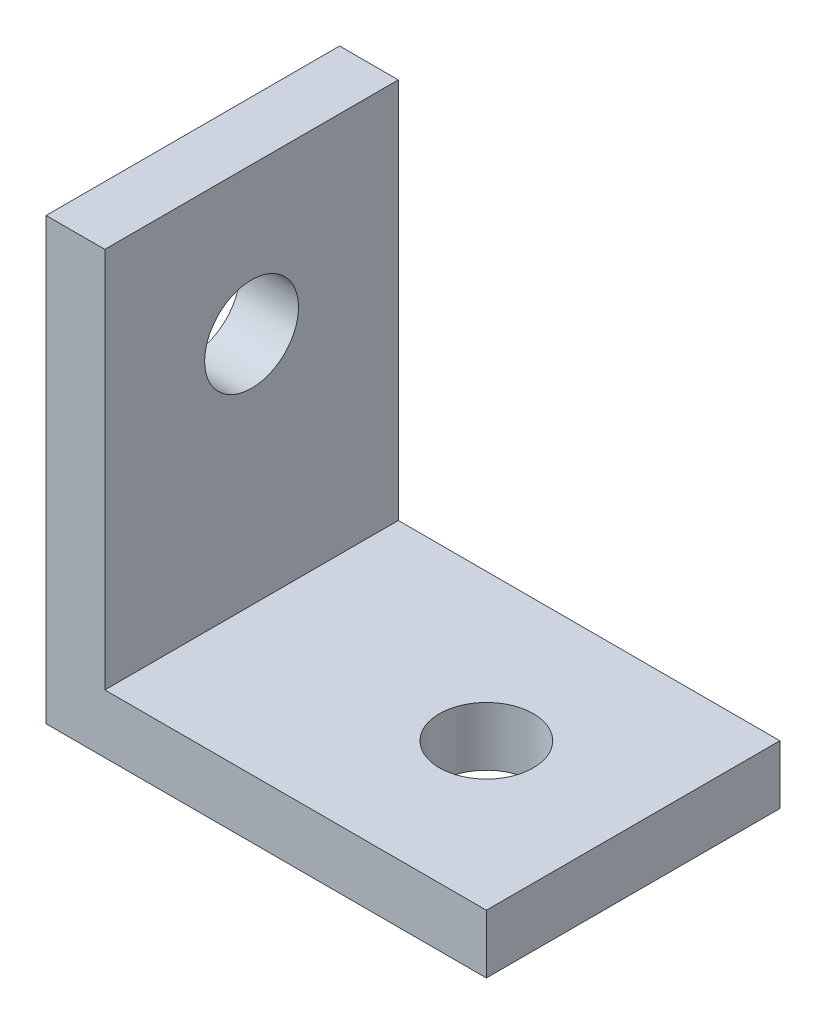
SolidWorks part; units mm, degrees
material "1060 Alloy"
ref_plane "Front Plane" through (0, 0, 0) normal (0, 0, 1) x (1, 0, 0)
ref_plane "Top Plane" through (0, 0, 0) normal (0, 1, 0) x (1, 0, 0)
ref_plane "Right Plane" through (0, 0, 0) normal (1, 0, 0) x (0, 0, -1)
sketch "Sketch1" plane through (0, 0, 0) normal (0, 0, 1) x (1, 0, 0)
  line L0 (0, 0) -> (0, 15)
  line L1 (0, 15) -> (2, 15)
  line L2 (2, 15) -> (2, 2)
  line L3 (2, 2) -> (15, 2)
  line L4 (15, 2) -> (15, 0)
  line L5 (15, 0) -> (0, 0)
  dimension "D1" = 2
  dimension "D2" = 15
extrude "Base" add sketch "Sketch1" along normal mid plane 10
hole_wizard "Ø3.2 (3.2) Diameter Hole1" positions "3DSketch1" profile "Sketch2" hole size "Ø3.2" standard "ANSI Metric" end condition through all
sketch3d "3DSketch1"
  line L0 (0, 0, 5) -> (0, 0, -5) construction
  point P0 (0, 10, 0)
  point P2 (10, 0, 0)
  point P5 (0, 0, 0)
  point P7 (0, 0, 0)
  point P8 (0, 0, 0)
  dimension "D1" = 10
  dimension "D2" = 10
sketch "Sketch2" plane through (0, 10, 0) normal (0, 1, 0) x (0, 0, 1)
  line L0 (0, 0) -> (0, 15)
  line L1 (0, 15) -> (1.6, 15)
  line L2 (1.6, 15) -> (1.6, 0)
  line L5 (1.6, 0) -> (0, 0)
  line L11 (0, -6.35) -> (0, 107.95) construction
  dimension "Thru Hole Dia." = 3.2
  dimension "Thru Hole Depth" = 15
